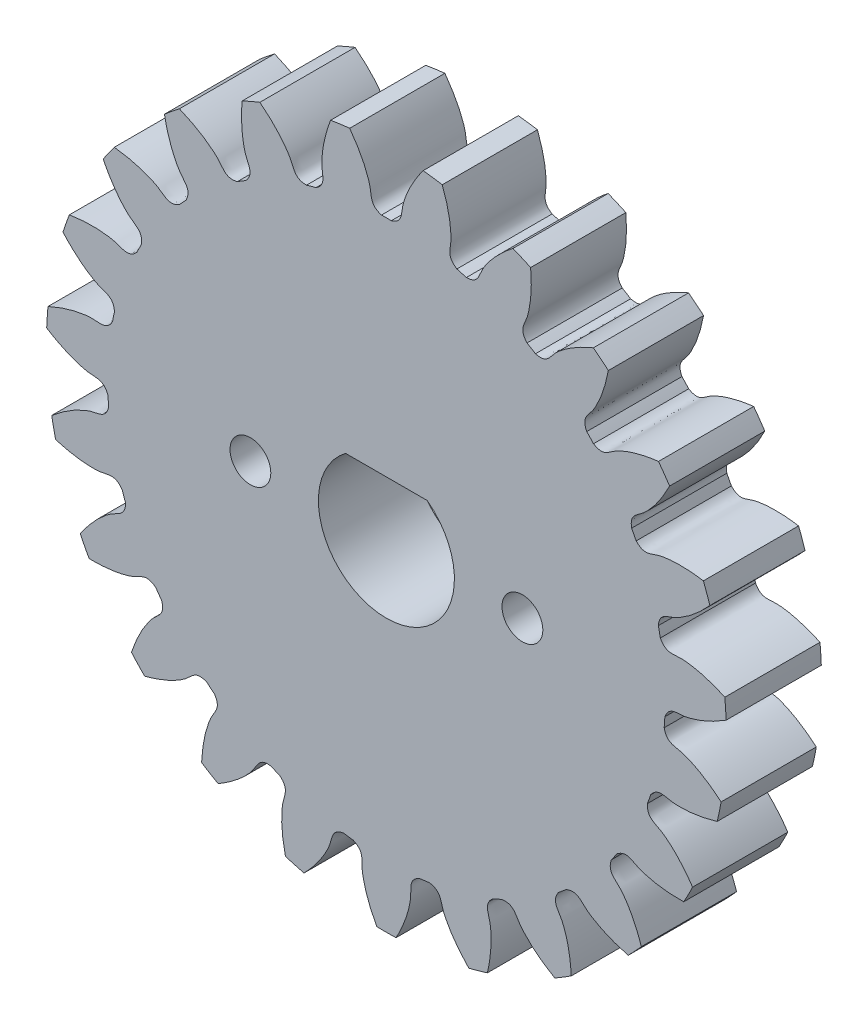
SolidWorks part; units mm, degrees
material "6061 合金"
ref_plane "前视基准面" through (0, 0, 0) normal (0, 0, 1) x (1, 0, 0)
ref_plane "上视基准面" through (0, 0, 0) normal (0, 1, 0) x (1, 0, 0)
ref_plane "右视基准面" through (0, 0, 0) normal (1, 0, 0) x (0, 0, -1)
sketch "草图1" plane through (0, 0, 0) normal (0, 0, 1) x (1, 0, 0)
  circle A0 centre (0, 0) radius 25
extrude "凸台-拉伸1" add sketch "草图1" along normal blind 7
ref_axis "基准轴1" through (0, 0, 7) along (0, 0, -1)
sketch "草图2" plane through (0, 0, 0) normal (0, 0, 1) x (1, 0, 0)
  line L0 (0, 0) -> (0, 25) construction
  circle A0 centre (0, 0) radius 25 construction
  arc A1 (0.3628, 20.4968) -> (-0.3628, 20.4968) centre (0, 0) ccw
  arc A2 (6.3634, 28.3724) -> (-6.3634, 28.3724) centre (0, 0) ccw
  spline S0 degree 3 poles (0.3628, 20.4968) (1.1555, 20.7335) (1.0875, 21.2677) (1.1859, 21.7944) (1.199, 21.8578) (1.2153, 21.9295) (1.2352, 22.0092) (1.2588, 22.0968) (1.2867, 22.1923) (1.319, 22.2954) (1.3562, 22.4061) (1.3984, 22.5241) (1.4461, 22.6493) (1.4995, 22.7816) (1.5589, 22.9207) (1.6247, 23.0665) (1.6971, 23.2188) (1.7763, 23.3773) (1.8628, 23.5419) (1.9567, 23.7122) (2.0583, 23.8882) (2.1678, 24.0695) (2.2856, 24.2558) (2.4119, 24.447) (2.5468, 24.6427) (2.6907, 24.8428) (2.8438, 25.0468) (3.0062, 25.2545) (3.1782, 25.4657) (3.36, 25.6799) (3.5517, 25.897) (3.7537, 26.1165) (3.9659, 26.3382) (4.1886, 26.5618) (4.422, 26.7868) (4.6662, 27.013) (4.9213, 27.24) (5.1875, 27.4675) (5.4648, 27.6952) (5.8542, 28.0019) (6.1566, 28.2256) (6.3634, 28.3724) knots 0 0 0 0 0.147387 0.15296 0.159389 0.166677 0.174821 0.183823 0.193683 0.204399 0.215973 0.228404 0.241693 0.255839 0.270842 0.286703 0.303421 0.320996 0.339428 0.358718 0.378866 0.39987 0.421732 0.444451 0.468028 0.492462 0.517753 0.543901 0.570907 0.59877 0.627491 0.657069 0.687504 0.718796 0.750946 0.783953 0.817818 0.85254 0.888119 0.924555 1 1 1 1
  spline S1 degree 3 poles (-0.3628, 20.4968) (-1.1555, 20.7335) (-1.0875, 21.2677) (-1.1859, 21.7944) (-1.199, 21.8578) (-1.2153, 21.9295) (-1.2352, 22.0092) (-1.2588, 22.0968) (-1.2867, 22.1923) (-1.319, 22.2954) (-1.3562, 22.4061) (-1.3984, 22.5241) (-1.4461, 22.6493) (-1.4995, 22.7816) (-1.5589, 22.9207) (-1.6247, 23.0665) (-1.6971, 23.2188) (-1.7763, 23.3773) (-1.8628, 23.5419) (-1.9567, 23.7122) (-2.0583, 23.8882) (-2.1678, 24.0695) (-2.2856, 24.2558) (-2.4119, 24.447) (-2.5468, 24.6427) (-2.6907, 24.8428) (-2.8438, 25.0468) (-3.0062, 25.2545) (-3.1782, 25.4657) (-3.36, 25.6799) (-3.5517, 25.897) (-3.7537, 26.1165) (-3.9659, 26.3382) (-4.1886, 26.5618) (-4.422, 26.7868) (-4.6662, 27.013) (-4.9213, 27.24) (-5.1875, 27.4675) (-5.4648, 27.6952) (-5.8542, 28.0019) (-6.1566, 28.2256) (-6.3634, 28.3724) knots 0 0 0 0 0.147387 0.15296 0.159389 0.166677 0.174821 0.183823 0.193683 0.204399 0.215973 0.228404 0.241693 0.255839 0.270842 0.286703 0.303421 0.320996 0.339428 0.358718 0.378866 0.39987 0.421732 0.444451 0.468028 0.492462 0.517753 0.543901 0.570907 0.59877 0.627491 0.657069 0.687504 0.718796 0.750946 0.783953 0.817818 0.85254 0.888119 0.924555 1 1 1 1
extrude "切除-拉伸1" cut sketch "草图2" along normal through all
pattern_circular "阵列(圆周)1" count 23 every 15.652 about axis through (0, 0, 7) along (0, 0, -1) of "切除-拉伸1"
sketch "草图3" plane through (0, 0, 0) normal (0, 0, 1) x (1, 0, 0)
  circle A0 centre (0, 0) radius 23 construction
  dimension "Dn" = 46
sketch "草图4" plane through (0, 0, 7) normal (0, 0, 1) x (1, 0, 0)
  line L0 (0, 0) -> (0, 4) construction
  line L1 (-3, 4) -> (3, 4)
  arc A0 (-3, 4) -> (3, 4) centre (0, 0) ccw
  dimension "D1" = 10
  dimension "D2" = 4
extrude "切除-拉伸2" cut sketch "草图4" against normal blind 7
sketch "草图9" plane through (0, 0, 0) normal (0, 0, -1) x (-1, 0, 0)
  line L0 (0, 29.8806) -> (0, -35.3045) construction
  line L1 (-33.3968, 0) -> (32.0219, 0) construction
  circle A0 centre (-10, 0) radius 1.5
  circle A2 centre (10, 0) radius 1.5
  dimension "D1" = 10
  dimension "D2" = 3
extrude "切除-拉伸3" cut sketch "草图9" against normal through all
chamfer "倒角1" distance 1.5 angle 45 2 edges at (8.5, 0, 0) (-8.5, 0, 0)
